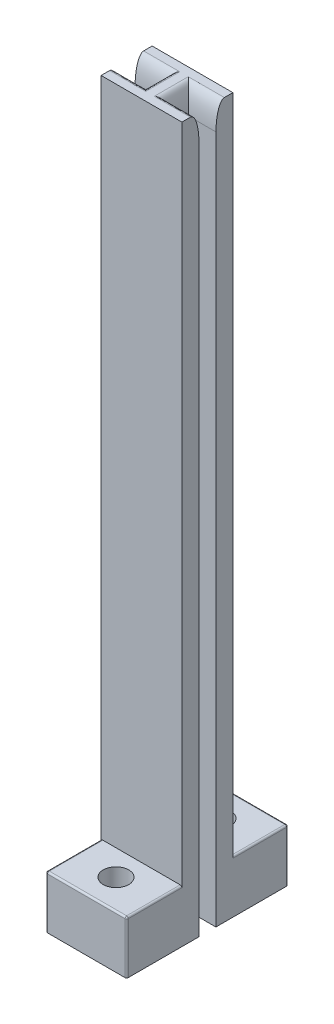
SolidWorks part; units mm, degrees
note: The reader was unsure of these and kept them because the rebuilt part matched: shared geometry of "Sketch1<3>".
ref_plane "Front Plane" through (0, 0, 0) normal (0, 0, 1) x (1, 0, 0)
ref_plane "Top Plane" through (0, 0, 0) normal (0, 1, 0) x (1, 0, 0)
ref_plane "Right Plane" through (0, 0, 0) normal (1, 0, 0) x (0, 0, -1)
sketch "Sketch1" plane through (0, 0, 0) normal (0, 1, 0) x (1, 0, 0)
  line L0 (0, 0) -> (0, 8.5)
  line L1 (0, 8.5) -> (3.25, 8.5)
  line L2 (3.25, 8.5) -> (3.25, 10.5)
  line L3 (3.25, 10.5) -> (0, 10.5)
  line L4 (0, 10.5) -> (0, 19)
  line L5 (0, 19) -> (9.5, 19)
  line L6 (9.5, 19) -> (9.5, 10.5)
  line L7 (9.5, 10.5) -> (6.25, 10.5)
  line L8 (6.25, 10.5) -> (6.25, 8.5)
  line L9 (6.25, 8.5) -> (9.5, 8.5)
  line L10 (9.5, 8.5) -> (9.5, 0)
  line L11 (9.5, 0) -> (0, 0)
  line L12 (0, 0) -> (0.3184, -0.0398)
  line L13 (0, 6.5) -> (9.5, 6.5)
  line L14 (0, 12.5) -> (9.5, 12.5)
  circle A0 centre (4.75, 15.5) radius 1.5
  circle A1 centre (4.75, 3.5) radius 1.5
  point P3 (1.625, 10.5)
  point P15 (6.25, 9.5)
  point P22 (4.75, 12.5)
  dimension "D17" = 3
  dimension "D19" = 3
  dimension "D1" = 8.5
  dimension "D2" = 10.5
  dimension "D3" = 19
  dimension "D4" = 8.5
  dimension "D5" = 2
  dimension "D6" = 9.5
  dimension "D7" = 3.25
  dimension "D8" = 6.25
  dimension "D9" = 3
  dimension "D10" = 3.25
  dimension "D11" = 6
  dimension "D12" = 6.5
  dimension "D13" = 2
  dimension "D14" = 2
  dimension "D15" = 2
  dimension "D16" = 4.75
  dimension "D18" = 3
extrude "Boss-Extrude1" add sketch "Sketch1" along normal blind 6.2 contours L13 L0 L11 L10 A1 | L4 L14 L6 L5 A0
extrude "Boss-Extrude2" add sketch "Sketch1<3>" along normal blind 84 contours L14 L4 L3 L2 L1 L0 L13 L10 L9 L8 L7 L6
sketch "Sketch1<3>" plane through (0, 0, 0) normal (0, 1, 0) x (1, 0, 0) same geometry as "Sketch1"
fillet "Fillet7" radius 1 4 edges at (1.625, 84, -8.5) (1.625, 84, -10.5) (7.875, 84, -8.5) (7.875, 84, -10.5)
fillet "Fillet8" radius 1 2 edges
fillet "Fillet9" radius 0.2 10 edges at (0, 3.1, 0) (0, 6.2, -3.25) (9.5, 3.1, 0) (4.75, 6.2, 0) (9.5, 6.2, -3.25) (0, 6.2, -15.75) (0, 3.1, -19) (9.5, 3.1, -19) (4.75, 6.2, -19) (9.5, 6.2, -15.75)
